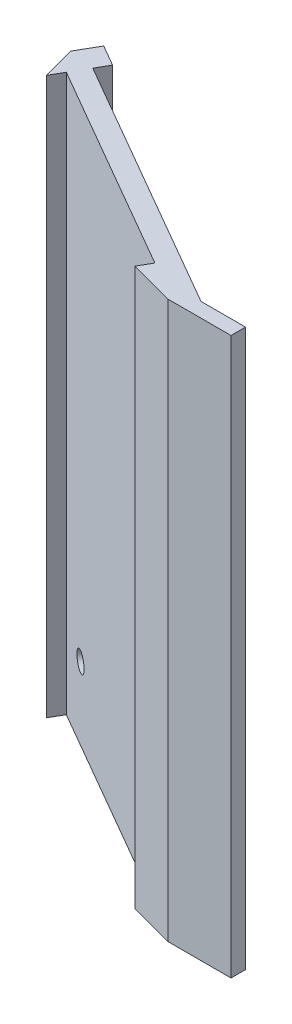
SolidWorks part; units mm, degrees
ref_plane "Plan de face" through (0, 0, 0) normal (0, 0, 1) x (1, 0, 0)
ref_plane "Plan de dessus" through (0, 0, 0) normal (0, 1, 0) x (1, 0, 0)
ref_plane "Plan de droite" through (0, 0, 0) normal (1, 0, 0) x (0, 0, -1)
sketch "Esquisse1" plane through (0, 0, 0) normal (0, 1, 0) x (1, 0, 0)
  line L0 (161.1651, -2.9953) -> (-1.8349, -2.9953) construction
  line L1 (-11.1651, -0.4953) -> (-1.8349, -2.9953)
  line L2 (-1.8349, -2.9953) -> (11.1651, -2.9953)
  line L3 (11.1651, -2.9953) -> (11.1651, 0.0047)
  line L4 (11.1651, 0.0047) -> (1.9689, 0.0047)
  line L5 (-55.2965, 33.0669) -> (-53.7965, 35.6649)
  line L7 (-11.1651, -0.4953) -> (-9.6651, 2.1028)
  line L8 (-54.4663, 24.5047) -> (-56.2965, 31.3348)
  line L9 (-9.6651, 2.1028) -> (-52.9663, 27.1028)
  line L11 (-7.6601, 5.564) -> (-50.9663, 30.5669)
  line L12 (-56.2965, 31.3348) -> (-55.2965, 33.0669)
  line L13 (-54.4663, 24.5047) -> (-52.9663, 27.1028)
  line L14 (-53.7965, 35.6649) -> (-49.4663, 33.1649)
  line L15 (-7.6601, 5.564) -> (1.9689, 0.0047)
  line L16 (-49.4663, 33.1649) -> (-50.9663, 30.5669)
  dimension "D1" = 7
  dimension "D2" = 5
  dimension "D3" = 5
extrude "Boss.-Extru.1" add sketch "Esquisse1" along normal blind 115 contours L4 L1 L2 L3 region at (-24.8594, 0, -13.4483)
sketch "Esquisse3" plane through (-1.5057, 0, 2.608) normal (-0.5, 0, 0.866) x (0.866, 0, 0.5)
  line L0 (-59.4216, 115) -> (-59.4216, 0) construction
  line L1 (-9.4216, 115) -> (-9.4216, 0) construction
  line L2 (-9.4216, 0) -> (-59.4216, 0) construction
  circle A0 centre (-51.4216, 15) radius 2
  circle A1 centre (-17.4216, 15) radius 2
  point P10 (0, 0)
  dimension "D1" = 4
  dimension "D2" = 8
  dimension "D3" = 8
  dimension "D4" = 15
extrude "Enlèv. mat.-Extru.1" cut sketch "Esquisse3" against normal blind 115
sketch "Esquisse4" plane through (0.4943, 0, -0.8561) normal (0.5, 0, -0.866) x (-0.866, 0, -0.5)
  line L0 (59.4216, 0) -> (-1.7028, 0) construction
  line L1 (19.731, 11) -> (22.0404, 15)
  line L2 (22.0404, 15) -> (19.731, 19)
  line L3 (19.731, 19) -> (15.1122, 19)
  line L4 (15.1122, 19) -> (12.8028, 15)
  line L5 (12.8028, 15) -> (15.1122, 11)
  line L6 (15.1122, 11) -> (19.731, 11)
  line L7 (49.1122, 11) -> (53.731, 11)
  line L8 (53.731, 11) -> (56.0404, 15)
  line L9 (56.0404, 15) -> (53.731, 19)
  line L10 (53.731, 19) -> (49.1122, 19)
  line L11 (49.1122, 19) -> (46.8028, 15)
  line L12 (46.8028, 15) -> (49.1122, 11)
  line L13 (9.4216, 0) -> (25.4216, 0)
  line L14 (9.4216, 0) -> (9.4216, 22)
  line L15 (9.4216, 22) -> (25.4216, 22)
  line L16 (25.4216, 0) -> (25.4216, 22)
  line L17 (9.4216, 0) -> (25.4216, 22) construction
  line L18 (9.4216, 22) -> (25.4216, 0) construction
  line L19 (59.4216, 115) -> (59.4216, 0) construction
  line L20 (43.4216, 0) -> (59.4216, 0)
  line L21 (43.4216, 0) -> (43.4216, 22)
  line L22 (43.4216, 22) -> (59.4216, 22)
  line L23 (59.4216, 0) -> (59.4216, 22)
  line L24 (43.4216, 0) -> (59.4216, 22) construction
  line L25 (43.4216, 22) -> (59.4216, 0) construction
  circle A0 centre (17.4216, 15) radius 4 construction
  circle A1 centre (51.4216, 15) radius 4 construction
  point P23 (17.4216, 11)
  point P29 (51.4216, 11)
  dimension "D1" = 8
  dimension "D2" = 8
  dimension "D3" = 22
  dimension "D4" = 8
  dimension "D5" = 16
  dimension "D6" = 8
extrude "Boss.-Extru.2" add sketch "Esquisse4" along normal up to surface (3 mm away) up to face at (-51.6314, 57.5, -34.4149)
fillet "Congé1" radius 3.5 6 edges at (-21.5215, 11, -13.5669) (-7.6651, 11, -5.5669) (-14.5933, 22, -9.5669) (-37.1099, 11, -22.5669) (-44.0381, 22, -26.5669) (-50.2163, 22, -31.8659)
